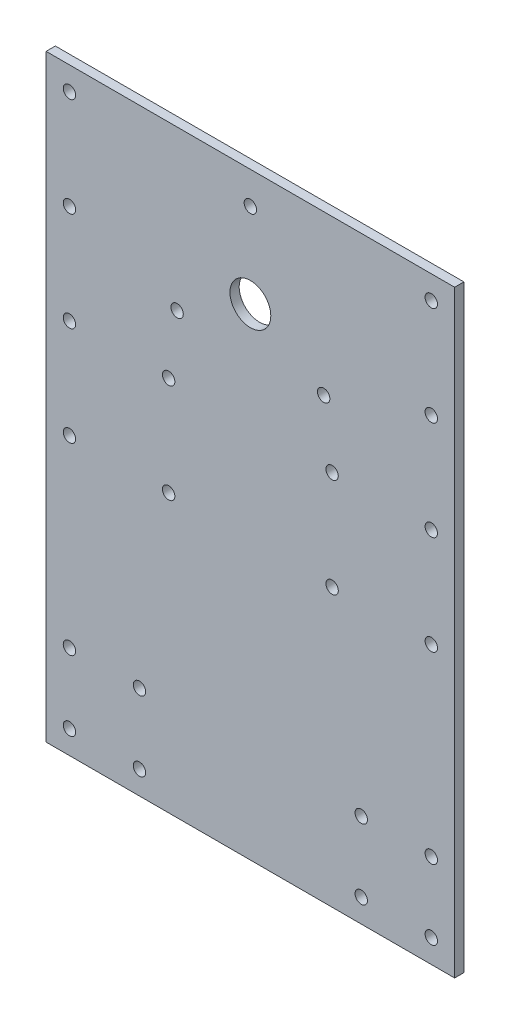
SolidWorks part; units mm, degrees
ref_plane "Front Plane" through (0, 0, 0) normal (0, 0, 1) x (1, 0, 0)
ref_plane "Top Plane" through (0, 0, 0) normal (0, 1, 0) x (1, 0, 0)
ref_plane "Right Plane" through (0, 0, 0) normal (1, 0, 0) x (0, 0, -1)
sketch "Sketch1" plane through (0, 0, 0) normal (0, 0, 1) x (1, 0, 0)
  line L0 (0, 102.5) -> (0, -102.5) construction
  line L1 (-70, -102.5) -> (70, -102.5)
  line L2 (-70, -102.5) -> (-70, 102.5)
  line L3 (-70, 102.5) -> (70, 102.5)
  line L4 (70, -102.5) -> (70, 102.5)
  line L5 (-70, -102.5) -> (70, 102.5) construction
  line L6 (-70, 102.5) -> (70, -102.5) construction
  line L7 (-50, -98.3304) -> (-50, -80.5714) construction
  line L10 (-62, -82.5) -> (-36.3402, -82.5) construction
  circle A0 centre (0, 62.5) radius 33.35 construction
  circle A1 centre (0, 62.5) radius 29 construction
  circle A2 centre (0, 91.5) radius 2.125
  circle A3 centre (25.1147, 48) radius 2.125
  circle A4 centre (-25.1147, 48) radius 2.125
  circle A10 centre (0, 62.5) radius 7
  circle A11 centre (-62, -94.5) radius 2.125
  circle A12 centre (-38, -94.5) radius 2.125
  circle A13 centre (-38, -70.5) radius 2.125
  circle A14 centre (-62, -70.5) radius 2.125
  circle A15 centre (38, -94.5) radius 2.125
  circle A16 centre (62, -94.5) radius 2.125
  circle A17 centre (62, -70.5) radius 2.125
  circle A18 centre (38, -70.5) radius 2.125
  point P0 (0, 0)
  point P19 (0, 62.5)
  dimension "D3" = 66.7
  dimension "D4" = 40
  dimension "D5" = 58
  dimension "D6" = 4.25
  dimension "D8" = 4.25
  dimension "D9" = 8
  dimension "D10" = 8
  dimension "D12" = 14
  dimension "D1" = 140
  dimension "D2" = 205
  dimension "D11" = 12
  dimension "D13" = 12
  dimension "D7" = 3
extrude "Boss-Extrude1" add sketch "Sketch1" along normal blind 3.175
sketch "Sketch2" plane through (0, 0, 3.175) normal (0, 0, 1) x (1, 0, 0)
  line L0 (70, 102.5) -> (-70, 102.5) construction
  line L1 (-70, 102.5) -> (-70, -102.5) construction
  line L2 (0, 102.5) -> (0, -102.5) construction
  line L3 (-70, -102.5) -> (70, -102.5) construction
  circle A0 centre (-62, 94.5) radius 2.125
  circle A1 centre (-62, 60.5) radius 2.125
  circle A2 centre (-62, 26.5) radius 2.125
  circle A3 centre (-62, -7.5) radius 2.125
  circle A4 centre (-28, 26.5) radius 2.125
  circle A5 centre (-28, -7.5) radius 2.125
  circle A6 centre (28, -7.5) radius 2.125
  circle A7 centre (28, 26.5) radius 2.125
  circle A8 centre (62, -7.5) radius 2.125
  circle A9 centre (62, 26.5) radius 2.125
  circle A10 centre (62, 60.5) radius 2.125
  circle A11 centre (62, 94.5) radius 2.125
  dimension "D1" = 4.25
  dimension "D2" = 8
  dimension "D3" = 8
  dimension "D4" = 4
  dimension "D5" = 2
extrude "Cut-Extrude1" cut sketch "Sketch2" against normal through all
